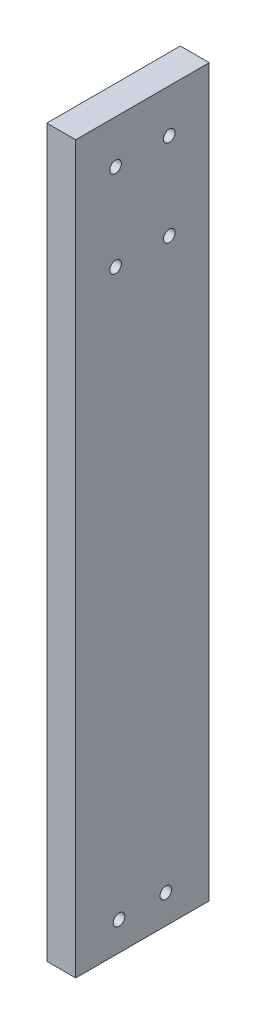
SolidWorks part; units mm, degrees
material "6061 Alloy"
ref_plane "Front Plane" through (0, 0, 0) normal (0, 0, 1) x (1, 0, 0)
ref_plane "Top Plane" through (0, 0, 0) normal (0, 1, 0) x (1, 0, 0)
ref_plane "Right Plane" through (0, 0, 0) normal (1, 0, 0) x (0, 0, -1)
sketch "Sketch1" plane through (0, 0, 0) normal (0, 1, 0) x (1, 0, 0)
  line L1 (0, 0) -> (12.7, 0)
  line L2 (0, 0) -> (0, 58.674)
  line L3 (0, 58.674) -> (12.7, 58.674)
  line L4 (12.7, 0) -> (12.7, 58.674)
  dimension "D1" = 58.674
  dimension "D2" = 12.7
extrude "Boss-Extrude1" add sketch "Sketch1" against normal blind 319.024
sketch "Sketch3" plane through (0, 0, 0) normal (-1, 0, 0) x (0, 0, 1)
  line L0 (0, -319.024) -> (0, -306.324) construction
  line L1 (0, -319.024) -> (0, 0) construction
  line L2 (0, -306.324) -> (-19.05, -306.324) construction
  line L3 (-29.337, -319.024) -> (-29.337, 0) construction
  line L4 (-58.674, -319.024) -> (0, -319.024) construction
  line L5 (-58.674, 0) -> (0, 0) construction
  line L6 (-58.674, -306.324) -> (-39.624, -306.324) construction
  line L7 (-58.674, -319.024) -> (-58.674, -306.324) construction
  line L8 (-58.674, -319.024) -> (-58.674, 0) construction
  line L9 (-58.674, 0) -> (-58.674, -76.2)
  point P15 (-41.148, -19.05)
  point P16 (-17.526, -19.05)
  point P17 (-17.526, -57.15)
  point P18 (-41.148, -57.15)
  dimension "D1" = 12.7
  dimension "D2" = 19.05
  dimension "D3" = 17.526
  dimension "D4" = 19.05
  dimension "D5" = 76.2
  dimension "D6" = 17.526
  dimension "D7" = 19.05
hole_wizard "1/4-20 Tapped Hole1" positions "3DSketch1" profile "Sketch4" tap size "1/4-20" standard "ANSI Inch" end condition through all
sketch3d "3DSketch1"
  point P0 (0, -306.324, -19.05)
  point P4 (0, -306.324, -39.624)
  point P8 (0, -19.05, -41.148)
  point P11 (0, -19.05, -17.526)
  point P14 (0, -57.15, -41.148)
  point P17 (0, -57.15, -17.526)
sketch "Sketch4" plane through (0, -306.324, -19.05) normal (0, 1, 0) x (0, 0, 1)
  line L0 (0, 0) -> (0, 12.7)
  line L1 (0, 12.7) -> (2.5527, 12.7)
  line L2 (2.5527, 12.7) -> (2.5527, 0)
  line L5 (2.5527, 0) -> (0, 0)
  line L11 (0, -6.35) -> (0, 107.95) construction
  dimension "Thru Tap Drill Dia." = 5.1054
  dimension "Thru Tap Drill Depth" = 12.7
cosmetic thread "Hole Thread1" parameters "D2"=6.35
cosmetic thread "Hole Thread2" parameters "D2"=6.35
cosmetic thread "Hole Thread3" parameters "D2"=6.35
cosmetic thread "Hole Thread4" parameters "D2"=6.35
cosmetic thread "Hole Thread5" parameters "D2"=6.35
cosmetic thread "Hole Thread6" parameters "D2"=6.35
